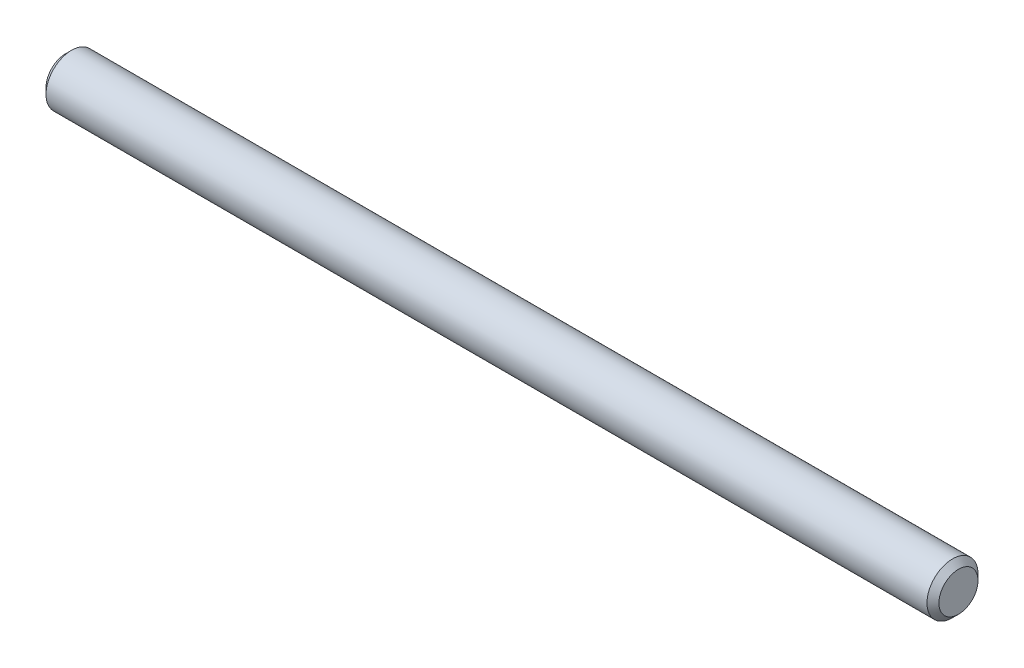
SolidWorks part; units mm, degrees
material "AISI 304"
ref_plane "Front Plane" through (0, 0, 0) normal (0, 0, 1) x (1, 0, 0)
ref_plane "Top Plane" through (0, 0, 0) normal (0, 1, 0) x (1, 0, 0)
ref_plane "Right Plane" through (0, 0, 0) normal (1, 0, 0) x (0, 0, -1)
sketch "Sketch1" plane through (0, 0, 0) normal (0, 0, 1) x (1, 0, 0)
  line L0 (-70, 0) -> (70, 0) construction
  line L1 (70, 4) -> (70, -4) construction
  line L2 (-70, 4) -> (-70, -4) construction
  point P6 (65.625, -4)
  dimension "Thread Diameter" = 8
  dimension "Length" = 140
  dimension "D1" = 4.375
sketch "Sketch2" plane through (0, 0, 0) normal (1, 0, 0) x (0, 0, -1)
  circle A0 centre (0, 0) radius 4
extrude "Boss-Extrude1" add sketch "Sketch2" against normal up to vertex (70 mm away) and the other way up to vertex (70 mm away) up to point (-70, 0, 0) other way up to point (70, 0, 0)
sketch "Sketch3" plane through (70, 0, 0) normal (1, 0, 0) x (0, 0, -1)
  circle A1 centre (0, 0) radius 4
  circle A2 centre (0, 0) radius 4
  dimension "D1" = 0
curve "Helix/Spiral1" [suppressed] parameters "Pitch"=1.25
chamfer "Chamfer1" distance 0.9375 angle 45 2 edges at (-70, 0, -4) (70, 0, -4)
sketch "Sketch4" plane through (0, 0, 0) normal (0, 0, 1) x (1, 0, 0)
  line L0 (69.9219, 4.1353) -> (70.5469, 3.0528) construction
  line L1 (70.5469, 3.0528) -> (71.1719, 4.1353) construction
  line L2 (71.1719, 4.1353) -> (69.9219, 4.1353) construction
  line L3 (70.5469, 4.1353) -> (70.5469, 4) construction
  line L4 (70.5469, 3.0528) -> (70.5469, 3.1881) construction
  line L5 (70.4688, 3.1881) -> (70.625, 3.1881) construction
  line L6 (70, 4) -> (71.0938, 4) construction
  line L7 (70.4688, 3.1881) -> (69.9609, 4.0677)
  line L8 (70.4688, 3.1881) -> (70.625, 3.1881)
  line L9 (69.9609, 4.0677) -> (71.1328, 4.0677)
  line L10 (71.1328, 4.0677) -> (70.625, 3.1881)
  point P13 (70.5469, 4.0677)
  dimension "D2" = 0.1562
sweep "Cut-Sweep3" [suppressed] cut profiles "Sketch4" path "Helix/Spiral1"
move or copy body "Body-Move/Copy1" [suppressed] bodies to move or copy 101
equation "\"D3@Helix/Spiral1\" = \"Length@Sketch1\"+\"Pitch@Helix/Spiral1\""
equation "\"D1@Chamfer1\" = \"Pitch@Helix/Spiral1\"*.75"
equation "\"D1@Sketch4\" = \"Pitch@Helix/Spiral1\""
equation "\"D2@Sketch4\" = \"D1@Sketch4\"/8"
equation "\"D1@Sketch1\" = \"Pitch@Helix/Spiral1\"*3.50"
